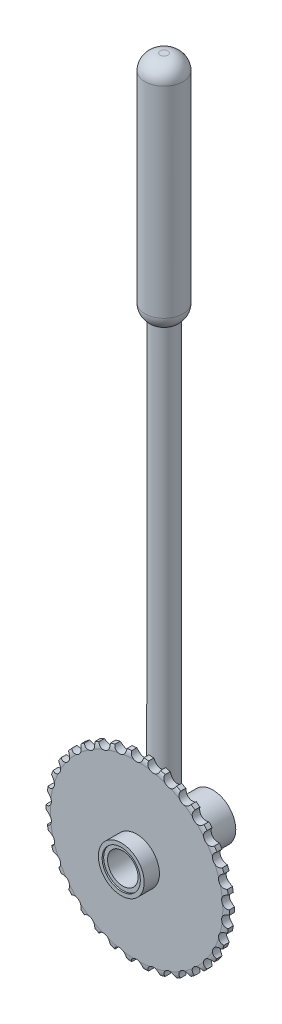
SolidWorks part; units mm, degrees
material "1060 Alloy"
ref_plane "Front Plane" through (0, 0, 0) normal (0, 0, 1) x (1, 0, 0)
ref_plane "Top Plane" through (0, 0, 0) normal (0, 1, 0) x (1, 0, 0)
ref_plane "Right Plane" through (0, 0, 0) normal (1, 0, 0) x (0, 0, -1)
sketch "Sketch1" plane through (0, 0, 0) normal (0, 0, 1) x (1, 0, 0)
  circle A0 centre (0, 0) radius 15
  dimension "D1" = 30
extrude "Extrude1" add sketch "Sketch1" against normal blind 60
ref_plane "Plane4" through (0, 0, -10) normal (0, 0, 1) x (1, 0, 0)
sketch "Sketch2" plane through (0, 0, -10) normal (0, 0, 1) x (1, 0, 0)
  circle A0 centre (0, 0) radius 60
  dimension "D1" = 120
extrude "Extrude2" add sketch "Sketch2" against normal blind 5
ref_plane "Plane5" through (0, 0, 10) normal (0, 0, 1) x (1, 0, 0)
ref_plane "Plane6" through (0, 0, -10) normal (0, 0, 1) x (1, 0, 0)
ref_plane "Plane7" through (0, 0, -25) normal (0, 0, 1) x (1, 0, 0)
sketch "Sketch3" plane through (0, 0, 0) normal (0, 1, 0) x (1, 0, 0)
  line L0 (0, 0) -> (0, 28) construction
  circle A0 centre (0, 28) radius 8
  dimension "D1" = 16
  dimension "D2" = 28
extrude "Boss-Extrude1" add sketch "Sketch3" along normal blind 449
sketch "Sketch4" plane through (0, 449, 0) normal (0, 1, 0) x (1, 0, 0)
  circle A0 centre (0, 28) radius 12.5
  dimension "D1" = 25
extrude "Boss-Extrude2" add sketch "Sketch4" against normal blind 150
fillet "Fillet2" radius 10 1 edges at (0, 449, -15.5)
fillet "Fillet3" radius 10 1 edges at (0, 299, -15.5)
sketch "Sketch5" plane through (0, 0, 0) normal (0, 0, 1) x (1, 0, 0)
  circle A0 centre (0, 0) radius 10
extrude "Cut-Extrude1" cut sketch "Sketch5" against normal blind 60
sketch "Sketch6" plane through (0, 0, 0) normal (0, 0, 1) x (1, 0, 0)
  circle A0 centre (0, 0) radius 12.5
extrude "Cut-Extrude2" cut sketch "Sketch6" against normal blind 1
sketch "Sketch7" plane through (0, 0, -10) normal (0, 0, 1) x (1, 0, 0)
  line L0 (0, 60) -> (0, 0) construction
  circle A0 centre (0, 60) radius 4
  circle A1 centre (0, 0) radius 60 construction
  circle A3 centre (11.025, 58.9784) radius 4
  circle A4 centre (21.6745, 55.9483) radius 4
  circle A5 centre (31.5859, 51.013) radius 4
  circle A6 centre (40.4217, 44.3405) radius 4
  circle A7 centre (47.881, 36.1581) radius 4
  circle A8 centre (53.7098, 26.7443) radius 4
  circle A9 centre (57.7095, 16.4198) radius 4
  circle A10 centre (59.7441, 5.5361) radius 4
  circle A11 centre (59.7441, -5.5361) radius 4
  circle A12 centre (57.7095, -16.4198) radius 4
  circle A13 centre (53.7098, -26.7443) radius 4
  circle A14 centre (47.881, -36.1581) radius 4
  circle A15 centre (40.4217, -44.3405) radius 4
  circle A16 centre (31.5859, -51.013) radius 4
  circle A17 centre (21.6745, -55.9483) radius 4
  circle A18 centre (11.025, -58.9784) radius 4
  circle A19 centre (0, -60) radius 4
  circle A20 centre (-11.025, -58.9784) radius 4
  circle A21 centre (-21.6745, -55.9483) radius 4
  circle A22 centre (-31.5859, -51.013) radius 4
  circle A23 centre (-40.4217, -44.3405) radius 4
  circle A24 centre (-47.881, -36.1581) radius 4
  circle A25 centre (-53.7098, -26.7443) radius 4
  circle A26 centre (-57.7095, -16.4198) radius 4
  circle A27 centre (-59.7441, -5.5361) radius 4
  circle A28 centre (-59.7441, 5.5361) radius 4
  circle A29 centre (-57.7095, 16.4198) radius 4
  circle A30 centre (-53.7098, 26.7443) radius 4
  circle A31 centre (-47.881, 36.1581) radius 4
  circle A32 centre (-40.4217, 44.3405) radius 4
  circle A33 centre (-31.5859, 51.013) radius 4
  circle A34 centre (-21.6745, 55.9483) radius 4
  circle A35 centre (-11.025, 58.9784) radius 4
  point P75 (0, 0)
  dimension "D1" = 8
  dimension "D2" = 34
extrude "Cut-Extrude3" cut sketch "Sketch7" against normal up to next (5 mm away)
sketch "Sketch8" plane through (0, 0, 0) normal (0, 1, 0) x (1, 0, 0)
  line L0 (51.8085, 10) -> (51.8085, 15) construction
  line L1 (51.8085, 12.5) -> (61.166, 12.5) construction
  line L3 (56.4873, 15) -> (56.4873, 15.7204)
  line L4 (56.4873, 15.7204) -> (61.6813, 15.7204)
  line L5 (61.6813, 15.7204) -> (61.6813, 8.2125)
  line L6 (61.6813, 8.2125) -> (56.4873, 8.2125)
  line L7 (56.4873, 8.2125) -> (56.4873, 10)
  ellipse E0 centre (56.4873, 12.5) end of major axis (61.166, 12.5) minor radius 2.5 (56.4873, 10) -> (56.4873, 15) ccw
revolve "Cut-Revolve2" cut sketch "Sketch8" angle 360 about axis through (0, 0, -60) along (0, 0, 1)
